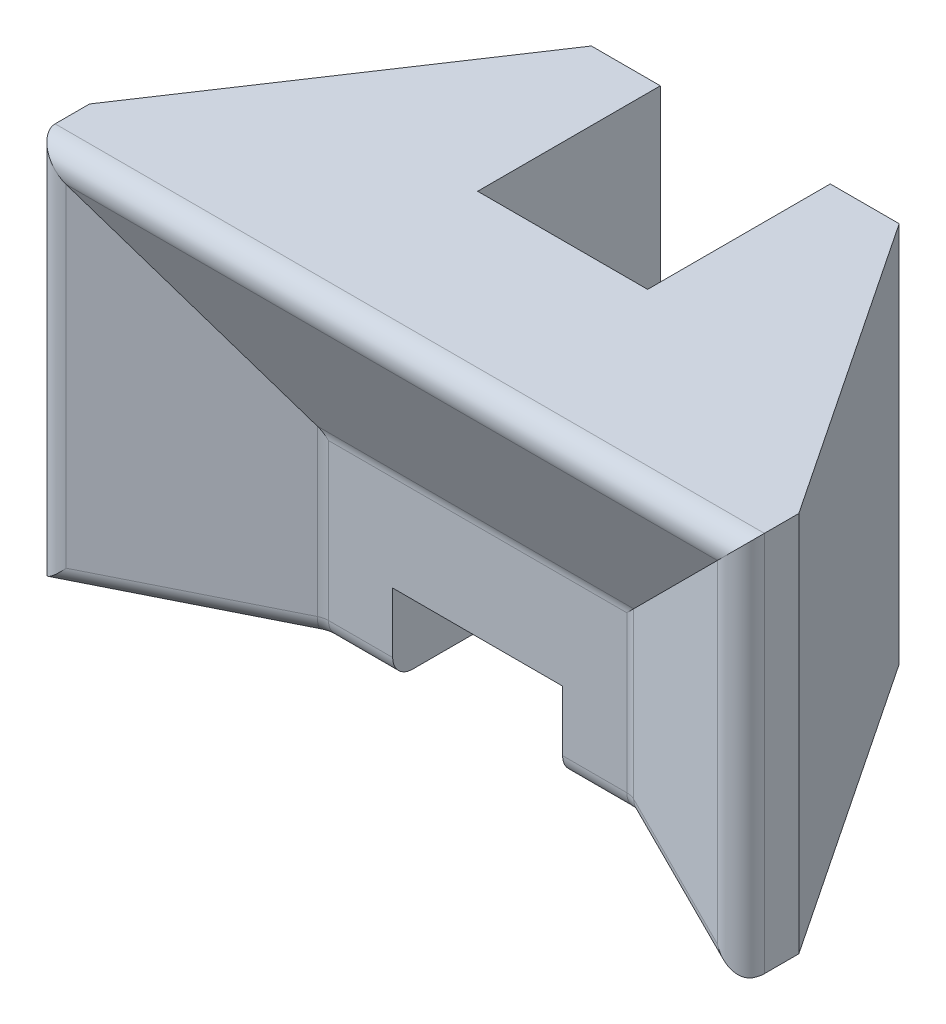
SolidWorks part; units mm, degrees
material "ABS"
ref_plane "Front Plane" through (0, 0, 0) normal (0, 0, 1) x (1, 0, 0)
ref_plane "Top Plane" through (0, 0, 0) normal (0, 1, 0) x (1, 0, 0)
ref_plane "Right Plane" through (0, 0, 0) normal (1, 0, 0) x (0, 0, -1)
sketch "Sketch1" plane through (0, 0, 0) normal (0, 0, 1) x (1, 0, 0)
  line L0 (23, -13.5) -> (53, -13.5)
  line L2 (-23, -13.5) -> (-23, 13.5)
  line L3 (-23, 13.5) -> (23, 13.5)
  line L4 (23, -13.5) -> (23, 13.5)
  line L5 (-23, -13.5) -> (23, 13.5) construction
  line L6 (-23, 13.5) -> (23, -13.5) construction
  line L7 (-53, -13.5) -> (-23, -13.5)
  line L8 (-53, -13.5) -> (-53, 43.5)
  line L9 (-53, 43.5) -> (53, 43.5)
  line L10 (53, -13.5) -> (53, 43.5)
  line L11 (-23, 13.5) -> (-23, 43.5) construction
  point P0 (0, 0)
  dimension "D1" = 46
  dimension "D2" = 30
  dimension "D3" = 27
extrude "Boss-Extrude1" add sketch "Sketch1" along normal blind 15
chamfer "Chamfer1" distance 15 distance2 30 3 edges at (23, 0, 15) (0, 13.5, 15) (-23, 0, 15) first distance on face at (23, 0, 7.5) first distance on face at (0, 13.5, 7.5) first distance on face at (-23, 0, 7.5)
sketch "Sketch4" plane through (0, 0, 0) normal (0, 0, -1) x (-1, 0, 0)
  line L1 (-53, 43.5) -> (53, 43.5)
  line L2 (-53, 43.5) -> (-53, -13.5)
  line L3 (-53, -13.5) -> (53, -13.5)
  line L4 (53, 43.5) -> (53, -13.5)
extrude "Boss-Extrude3" add sketch "Sketch4" along normal blind 40
sketch "Sketch5" plane through (0, -13.5, 0) normal (0, -1, 0) x (1, 0, 0)
  line L0 (23, 0) -> (-23, 0) construction
  line L1 (-12.7, 0) -> (12.7, 0)
  line L2 (-12.7, 0) -> (-12.7, -12.7)
  line L3 (-12.7, -12.7) -> (12.7, -12.7)
  line L4 (12.7, 0) -> (12.7, -12.7)
  line L5 (53, -40) -> (-53, -40) construction
  line L6 (-12.7, -12.7) -> (12.7, -12.7)
  line L7 (-12.7, -12.7) -> (-12.7, -40)
  line L8 (-12.7, -40) -> (12.7, -40)
  line L9 (12.7, -12.7) -> (12.7, -40)
  point P6 (0, 0)
  line M6 (-53, -40) -> (53, -40)
  line M9 (23, 0) -> (-23, 0)
  dimension "D1" = 25.4
  dimension "D2" = 12.7
extrude "Cut-Extrude3" cut sketch "Sketch5" against normal blind 12 contours L4 L2 L3 M9 region at (0, -13.5, -6.35)
extrude "Cut-Extrude4" cut sketch "Sketch5<3>" against normal through all contours L9 L3 L7 M6 region at (0, -13.5, -26.35)
sketch "Sketch5<3>" plane through (0, -13.5, 0) normal (0, -1, 0) x (1, 0, 0) same geometry as "Sketch5"
chamfer "Chamfer3" distance 45 distance2 30 2 edges at (53, 15, -40) (-53, 15, -40) first distance on face at (53, 15, -12.5) first distance on face at (-53, 15, -12.5)
fillet "Fillet2" radius 3 10 edges at (23, 0, 0) (0, 13.5, 0) (-23, 0, 0) (-38, -13.5, 7.5) (-17.85, -13.5, 0) (17.85, -13.5, 0) (38, -13.5, 7.5) (53, 15, 15) (0, 43.5, 15) (-53, 15, 15)
